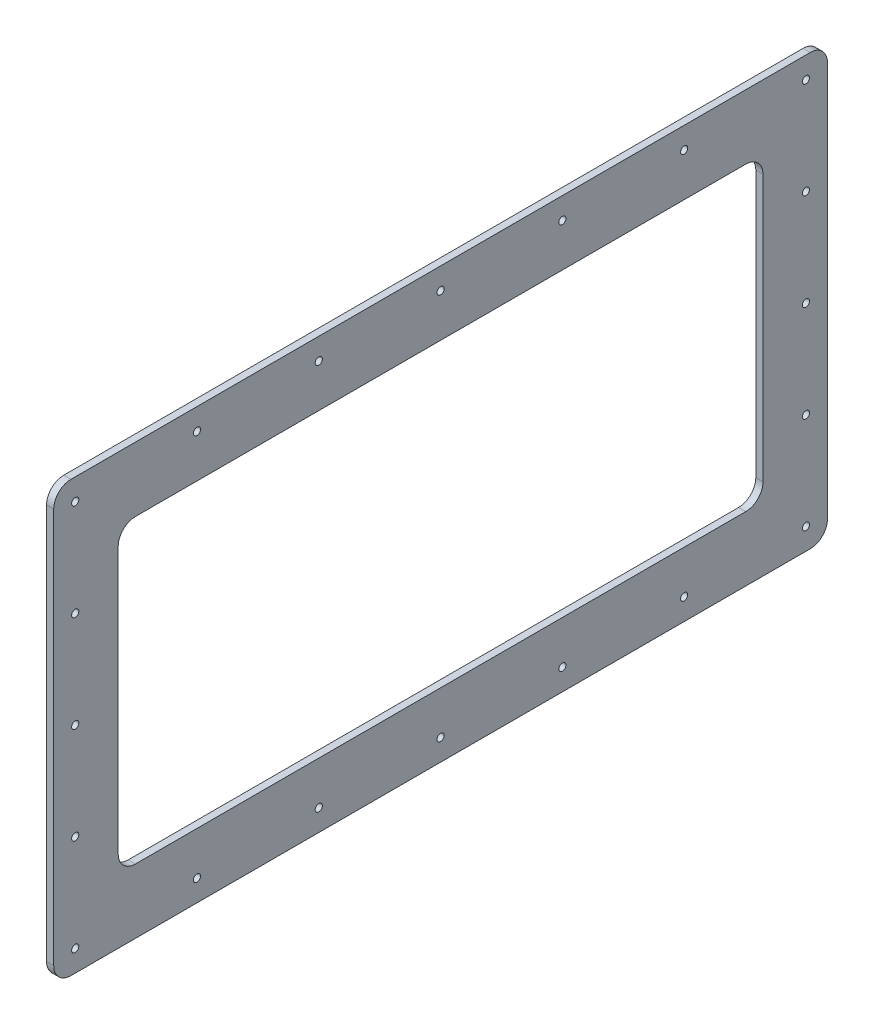
SolidWorks part; units mm, degrees
material "6061 Alloy"
ref_plane "Front Plane" through (0, 0, 0) normal (0, 0, 1) x (1, 0, 0)
ref_plane "Top Plane" through (0, 0, 0) normal (0, 1, 0) x (1, 0, 0)
ref_plane "Right Plane" through (0, 0, 0) normal (1, 0, 0) x (0, 0, -1)
sketch "Sketch1" plane through (-311.15, 0, 0) normal (-1, 0, 0) x (0, 0, 1)
  line L0 (285.75, 209.55) -> (285.75, 450.85) construction
  line L1 (-273.05, 196.85) -> (273.05, 196.85) construction
  line L2 (-285.75, 450.85) -> (-285.75, 209.55) construction
  line L3 (273.05, 463.55) -> (-273.05, 463.55) construction
  line L4 (285.75, 209.55) -> (285.75, 450.85) construction
  line L5 (-273.05, 196.85) -> (273.05, 196.85) construction
  line L6 (-285.75, 450.85) -> (-285.75, 209.55) construction
  line L7 (273.05, 463.55) -> (-273.05, 463.55) construction
  line L9 (-311.15, 488.95) -> (311.15, 488.95) construction
  line L10 (-311.15, 488.95) -> (-311.15, 171.45) construction
  line L11 (-311.15, 171.45) -> (311.15, 171.45) construction
  line L12 (311.15, 488.95) -> (311.15, 171.45) construction
  line L13 (-342.9, 520.7) -> (342.9, 520.7)
  line L14 (-342.9, 520.7) -> (-342.9, 139.7)
  line L15 (-342.9, 139.7) -> (342.9, 139.7)
  line L16 (342.9, 520.7) -> (342.9, 139.7)
  line L17 (-285.75, 463.55) -> (285.75, 463.55)
  line L18 (-285.75, 463.55) -> (-285.75, 196.85)
  line L19 (-285.75, 196.85) -> (285.75, 196.85)
  line L20 (285.75, 463.55) -> (285.75, 196.85)
  point P16 (0, 488.95)
  point P17 (0, 463.55)
  point P18 (-285.75, 330.2)
  point P19 (-311.15, 330.2)
  point P28 (0, 463.55)
  point P29 (0, 520.7)
  point P30 (-285.75, 330.2)
  point P31 (-342.9, 330.2)
  dimension "D1" = 622.3
  dimension "D2" = 317.5
  dimension "D3" = 31.75
  dimension "D4" = 31.75
  dimension "D5" = 25.4
  dimension "D6" = 25.4
extrude "Boss-Extrude1" add sketch "Sketch1" along normal blind 6.35 from offset 12.7
ref_plane "Plane1" through (0, 330.2, 0) normal (0, -1, 0) x (-1, 0, 0)
hole_wizard "1/4 (0.25) Diameter Hole1" positions "Sketch4" profile "Sketch3" hole size "1/4" standard "ANSI Inch" end condition through all
sketch "Sketch4" plane through (-330.2, 0, 0) normal (-1, 0, 0) x (0, 0, 1)
  line L6 (-285.75, 463.55) -> (-285.75, 196.85) construction
  line L7 (-285.75, 196.85) -> (285.75, 196.85) construction
  point P0 (-323.85, 158.75)
  dimension "D1" = 38.1
  dimension "D2" = 38.1
sketch "Sketch3" plane through (-330.2, 158.75, -323.85) normal (0, 1, 0) x (0, 0, 1)
  line L0 (0, 0) -> (0, 6.35)
  line L1 (0, 6.35) -> (3.175, 6.35)
  line L2 (3.175, 6.35) -> (3.175, 0)
  line L5 (3.175, 0) -> (0, 0)
  line L11 (0, -6.35) -> (0, 107.95) construction
  dimension "Thru Hole Dia." = 6.35
  dimension "Thru Hole Depth" = 6.35
pattern_linear "LPattern2" count 7 spacing 107.95 along (0, 0, 1) count 5 spacing 85.725 along (0, 1, 0) skipping (1, 1), (1, 2), (1, 3), (2, 1), (2, 2), (2, 3), (3, 1), (3, 2), (3, 3), (4, 1), (4, 2), (4, 3), (5, 1), (5, 2), (5, 3) of "1/4 (0.25) Diameter Hole1"
fillet "Fillet1" radius 15.24 8 edges at (-327.025, 196.85, 285.75) (-327.025, 463.55, 285.75) (-327.025, 196.85, -285.75) (-327.025, 139.7, 342.9) (-327.025, 139.7, -342.9) (-327.025, 520.7, 342.9) (-327.025, 463.55, -285.75) (-327.025, 520.7, -342.9)
equation "\"D3@LPattern2\"=25.5/6"
equation "\"D4@Sketch1\"=\"D3@Sketch1\""
equation "\"D2@Sketch4\"=\"D1@Sketch4\""
equation "\"D4@LPattern2\"=13.5/4"
